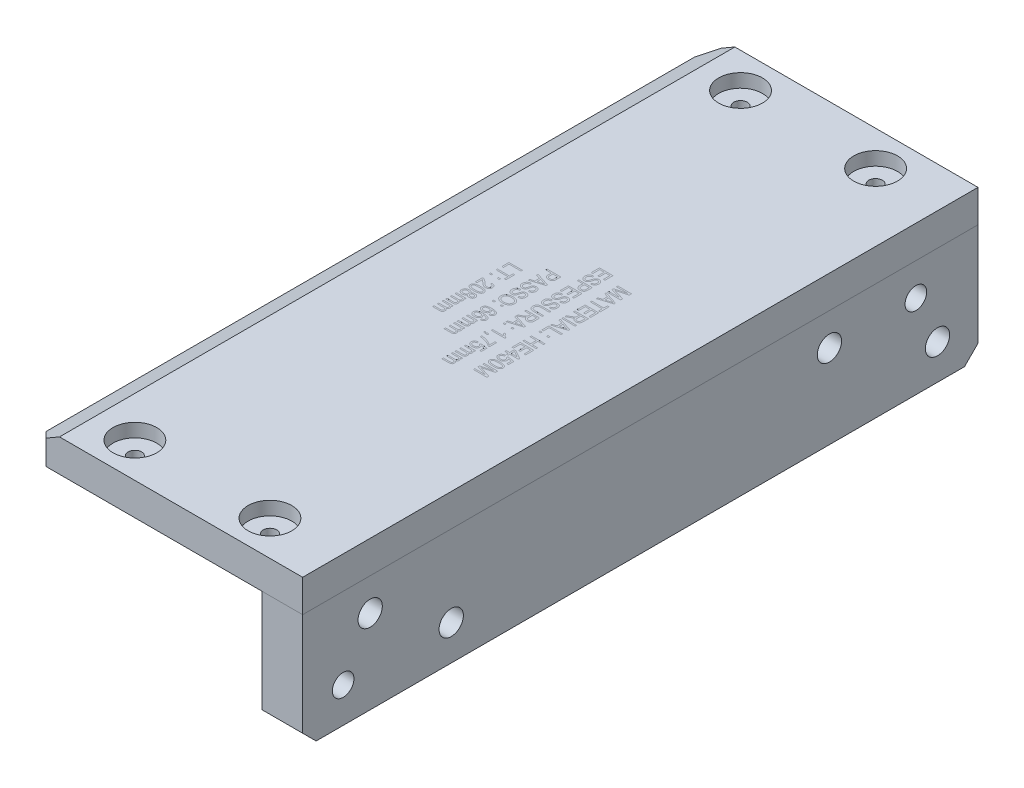
SolidWorks part; units mm, degrees
other "BASE"
other "FLANGE"
other "NERVURA"
other "Item de detalhe1"
other "Item de detalhe2"
other "Item de detalhe3"
other "Item de detalhe4"
other "Item de detalhe6"
other "Item de detalhe4"
other "Item de detalhe6"
other "Item de detalhe4"
other "Item de detalhe6"
other "Item de detalhe4"
other "Item de detalhe6"
other "Item de detalhe4"
other "Item de detalhe6"
other "Item de detalhe4"
other "Item de detalhe6"
other "Item de detalhe4"
other "Item de detalhe6"
other "Item de detalhe4"
other "Item de detalhe6"
other "Item de detalhe4"
other "Item de detalhe6"
other "Item de detalhe4"
other "Item de detalhe6"
other "Item de detalhe4"
other "Item de detalhe6"
other "Item de detalhe4"
other "Item de detalhe6"
other "Item de detalhe4"
other "Item de detalhe6"
other "Item de detalhe4"
other "Item de detalhe6"
other "Item de detalhe4"
other "Item de detalhe6"
other "Item de detalhe4"
other "Item de detalhe6"
other "Item de detalhe4"
other "Item de detalhe6"
other "Item de detalhe4"
other "Item de detalhe6"
other "Item de detalhe4"
other "Item de detalhe6"
other "Item de detalhe4"
other "Item de detalhe6"
other "Item de detalhe4"
other "Item de detalhe6"
other "Item de detalhe4"
other "Item de detalhe6"
other "Item de detalhe4"
other "Item de detalhe6"
other "Item de detalhe4"
other "Item de detalhe6"
other "Item de detalhe4"
other "Item de detalhe6"
other "Item de detalhe4"
other "Item de detalhe6"
other "Item de detalhe4"
other "Item de detalhe6"
other "Item de detalhe4"
other "Item de detalhe6"
other "Item de detalhe4"
other "Item de detalhe5"
other "Item de detalhe6"
other "Item de detalhe7"
material "SAE 1020"
ref_plane "Plano frontal" through (0, 0, 0) normal (0, 0, 1) x (1, 0, 0)
ref_plane "Plano superior" through (0, 0, 0) normal (0, 1, 0) x (1, 0, 0)
ref_plane "Plano direito" through (0, 0, 0) normal (1, 0, 0) x (0, 0, -1)
sketch "Esboço1" plane through (0, 0, 0) normal (0, 0, 1) x (1, 0, 0)
  line L1 (0, 0) -> (-100, 0)
  line L2 (0, 0) -> (0, -12)
  line L3 (0, -12) -> (-100, -12)
  line L4 (-100, 0) -> (-100, -12)
  dimension "D1" = 12
  dimension "D2" = 100
extrude "Ressalto-extrusão1" add sketch "Esboço1" along normal mid plane 250
sketch "Esboço2" plane through (0, 0, 0) normal (0, 0, 1) x (1, 0, 0)
  line L0 (0, 0) -> (-100, 0) construction
  line L1 (0, -12) -> (-15, -12)
  line L2 (0, -12) -> (0, -55)
  line L3 (0, -55) -> (-15, -55)
  line L4 (-15, -12) -> (-15, -55)
  dimension "D1" = 55
  dimension "D2" = 15
extrude "Ressalto-extrusão2" add sketch "Esboço2" along normal up to surface and the other way up to surface separate body contours L2 L3 L4 L1 up to face at (-50, -6, 125) other way up to face at (-50, -6, -125)
sketch "Esboço3" plane through (0, 0, 0) normal (0, 0, 1) x (1, 0, 0)
  line L0 (-100, -12) -> (-15, -12)
  line L1 (-15, -12) -> (-15, -55)
  line L2 (-15, -55) -> (-25, -55)
  line L3 (-25, -55) -> (-100, -17)
  line L4 (-100, -17) -> (-100, -12)
  dimension "D1" = 5
  dimension "D2" = 10
extrude "Ressalto-extrusão3" add sketch "Esboço3" along normal mid plane 6.35 separate body
sketch "Esboço5" plane through (0, 0, 0) normal (0, 1, 0) x (1, 0, 0)
  circle A0 centre (-75, -112.1) radius 8.1 construction
  circle A2 centre (-25, 112.1) radius 8.1 construction
  circle A3 centre (-75, 112.1) radius 8.1 construction
  circle A4 centre (-75, -112.1) radius 8.1
  circle A5 centre (-25, -112.1) radius 8.1
  circle A6 centre (-25, 112.1) radius 8.1
  circle A7 centre (-75, 112.1) radius 8.1
  circle A12 centre (-25, -112.1) radius 8.1 construction
extrude "Corte-extrusão2" cut sketch "Esboço5" against normal blind 5
hole_wizard "Furo roscado de M61" positions "Esboço7" profile "Esboço6" tap size "M6" standard "DIN"
sketch "Esboço7" plane through (0, -5, 0) normal (0, 1, 0) x (1, 0, 0)
  point P0 (-75, -112.1)
  point P3 (-25, -112.1)
  point P6 (-25, 112.1)
  point P9 (-75, 112.1)
sketch "Esboço6" plane through (-75, -5, 112.1) normal (1, 0, 0) x (0, 0, 1)
  line L0 (0, 0) -> (0, 19.5022)
  line L1 (0, 19.5022) -> (2.5, 18)
  line L2 (2.5, 18) -> (2.5, 0)
  line L5 (2.5, 0) -> (0, 0)
  line L10 (0, 19.5022) -> (-2.5, 18) construction
  line L11 (0, -6.35) -> (0, 107.95) construction
  dimension "Tap Drill Dia." = 5
  dimension "Tap Drill Depth" = 18
  dimension "Drill Angle" = 118
cosmetic thread "Rosca de furo6" parameters "D1"=10, "D2"=6
cosmetic thread "Rosca de furo7" parameters "D1"=10, "D2"=6
cosmetic thread "Rosca de furo8" parameters "D1"=10, "D2"=6
cosmetic thread "Rosca de furo9" parameters "D1"=10, "D2"=6
chamfer "Chanfro1" distance 10 angle 30 1 edges at (-100, 0, 0) first distance on face at (-83.1, 0, -112.1)
chamfer "Chanfro2" distance 5 angle 45 2 edges at (-7.5, -55, 125) (-7.5, -55, -125)
chamfer "Chanfro3" distance 5 angle 45 2 edges at (-100, -8.8868, 125) (-100, -8.8868, -125)
sketch "Esboço15" plane through (-15, 0, 0) normal (-1, 0, 0) x (0, 0, 1)
  line L0 (120, -55) -> (-120, -55) construction
  line L1 (-110, -42) -> (110, -42)
  line L2 (-110, -42) -> (-110, -24)
  line L3 (-110, -24) -> (110, -24)
  line L4 (110, -42) -> (110, -24)
  line L5 (125, -50) -> (125, -12) construction
  line L6 (-125, -12) -> (-125, -50) construction
  circle A0 centre (-110, -42) radius 7.5
  circle A1 centre (-102, -24) radius 4
  circle A2 centre (110, -24) radius 7.5
  circle A3 centre (110, -42) radius 4
  circle A4 centre (-70, -24) radius 7.5
  circle A7 centre (70, -42) radius 7.5
  dimension "D5" = 15
  dimension "D6" = 8
  dimension "D7" = 40
  dimension "D8" = 40
  dimension "D9" = 8
  dimension "D1" = 13
  dimension "D2" = 18
  dimension "D3" = 15
  dimension "D4" = 15
hole_wizard "Furo1" positions "Esboço16" profile "Esboço17" legacy end condition through all
sketch "Esboço16" plane through (-15, 0, 0) normal (-1, 0, 0) x (0, 0, 1)
  line L0 (110, -42) -> (110, -24) construction
  line L2 (-110, -24) -> (110, -24) construction
  point P0 (-110, -42)
  point P3 (70, -42)
  point P12 (-70, -24)
  point P15 (100, -24)
  dimension "D1" = 10
sketch "Esboço17" plane through (-15, -42, -110) normal (0, 1, 0) x (0, 0, 1)
  line L0 (0, 0) -> (0, 15)
  line L1 (0, 15) -> (4.5, 15)
  line L2 (4.5, 15) -> (4.5, 0)
  line L3 (4.5, 0) -> (0, 0)
  line L4 (0, 110) -> (0, -10) construction
  dimension "Diameter" = 9
  dimension "Depth" = 15
hole_wizard "Furos-guia com Ø8.0mm1" positions "Esboço18" profile "Esboço19" hole size "Ø8.0" standard "DIN" end condition through all
sketch "Esboço18" plane through (-15, 0, 0) normal (-1, 0, 0) x (0, 0, 1)
  circle A0 centre (110, -42) radius 4 construction
  point P0 (-102, -24)
  point P3 (110, -42)
sketch "Esboço19" plane through (-15, -24, -102) normal (0, 1, 0) x (0, 0, 1)
  line L0 (0, 0) -> (0, 15)
  line L1 (0, 15) -> (4, 15)
  line L2 (4, 15) -> (4, 0)
  line L5 (4, 0) -> (0, 0)
  line L11 (0, -6.35) -> (0, 107.95) construction
  dimension "Thru Hole Dia." = 8
  dimension "Thru Hole Depth" = 15
sketch "Esboço21" plane through (0, 0, 0) normal (0, 1, 0) x (1, 0, 0)
  line L0 (-35, -125) -> (-35, 125) construction
  line L1 (0, -125) -> (-90, -125) construction
  line L2 (0, 125) -> (-90, 125) construction
  line L3 (0, -125) -> (0, 125) construction
  text T0 "MATERIAL: HE450M\r\nESPESSURA: 1,75mm\r\nPASSO: 66mm\r\nLT: 208mm" font "Arial Narrow" height 5
  dimension "D1" = 35
extrude "Corte-extrusão3" cut sketch "Esboço21" against normal blind 0.001
sketch "Esboço20" [suppressed] plane through (0, 0, 3.175) normal (0, 0, 1) x (1, 0, 0)
  line L0 (-100, -9) -> (-12, -9)
  line L1 (-12, -9) -> (-12, -55)
  line L5 (-100, -12) -> (-100, -17)
  line L6 (-100, -17) -> (-25, -55)
  line L7 (-25, -55) -> (-15, -55)
  line L8 (-15, -55) -> (-15, -12)
  line L9 (-15, -12) -> (-100, -12)
  line L10 (-100, -9) -> (-100, -17)
  line L11 (-100, -17) -> (-25, -55)
  line L12 (-25, -55) -> (-12, -55)
  dimension "D2" = 3
  dimension "D3" = 3
  dimension "D4" = 88
  dimension "D5" = 46
  dimension "D1" = 0
extrude "Ressalto-extrusão4" [suppressed] add sketch "Esboço20" against normal blind 6.4 separate body
sketch "Esboço23" [suppressed] plane through (0, -12, 0) normal (0, -1, 0) x (1, 0, 0)
  line L6 (0, 125) -> (-95, 125)
  line L7 (-95, 125) -> (-100, 120)
  line L8 (-100, 120) -> (-100, -120)
  line L9 (-100, -120) -> (-95, -125)
  line L10 (-95, -125) -> (0, -125)
  line L11 (0, -125) -> (0, 125)
  line L12 (5, 125) -> (-95, 125)
  line L13 (-95, 125) -> (-100, 120)
  line L14 (-100, 120) -> (-100, -120)
  line L15 (-100, -120) -> (-95, -125)
  line L16 (-95, -125) -> (5, -125)
  line L17 (5, -125) -> (5, 125)
  dimension "D2" = 105
  dimension "D3" = 105
  dimension "D4" = 250
  dimension "D1" = 0
extrude "Ressalto-extrusão5" [suppressed] add sketch "Esboço23" against normal blind 19.05 separate body
sketch "Esboço24" [suppressed] plane through (0, 0, 0) normal (1, 0, 0) x (0, 0, -1)
  line L0 (-125, -12) -> (125, -12) construction
  line L6 (-125, -12) -> (-125, -50)
  line L7 (-125, -50) -> (-120, -55)
  line L8 (-120, -55) -> (120, -55)
  line L9 (120, -55) -> (125, -50)
  line L10 (125, -50) -> (125, -12)
  line L11 (125, -12) -> (-125, -12)
  line L12 (-125, -7) -> (-125, -50)
  line L13 (-125, -50) -> (-120, -55)
  line L14 (-120, -55) -> (120, -55)
  line L15 (120, -55) -> (125, -50)
  line L16 (125, -50) -> (125, -7)
  line L17 (125, -7) -> (-125, -7)
  circle A0 centre (-100, -24) radius 4.5 construction
  circle A1 centre (-100, -24) radius 4.5
  circle A2 centre (70, -24) radius 4.5 construction
  circle A3 centre (70, -24) radius 4.5
  circle A4 centre (-70, -42) radius 4.5 construction
  circle A5 centre (110, -42) radius 4.5 construction
  circle A6 centre (-70, -42) radius 4.5
  circle A7 centre (110, -42) radius 4.5
  dimension "D2" = 5
  dimension "D3" = 48
  dimension "D1" = 0
extrude "Ressalto-extrusão6" [suppressed] add sketch "Esboço24" against normal blind 19.1 separate body
